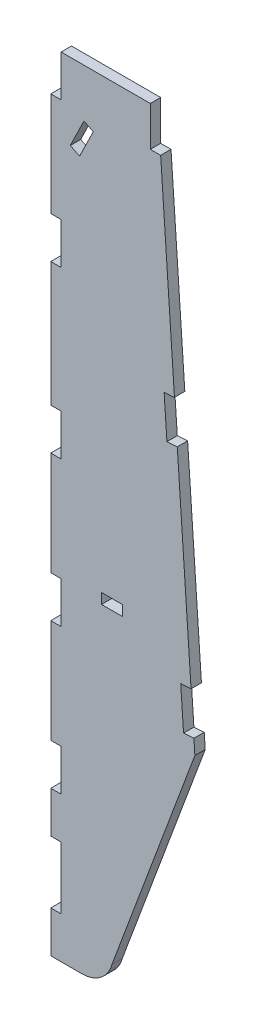
SolidWorks part; units mm, degrees
ref_plane "Plan de face" through (0, 0, 0) normal (0, 0, 1) x (1, 0, 0)
ref_plane "Plan de dessus" through (0, 0, 0) normal (0, 1, 0) x (1, 0, 0)
ref_plane "Plan de droite" through (0, 0, 0) normal (1, 0, 0) x (0, 0, -1)
sketch "Esquisse1" plane through (0, 0, 0) normal (0, 0, 1) x (1, 0, 0)
  line L0 (0, 0) -> (43, 0)
  line L1 (43, 0) -> (43, -19.1614)
  line L2 (43, -19.1614) -> (48, -19.1614)
  line L3 (48, -19.1614) -> (54.6543, -116.9352)
  line L4 (54.6543, -116.9352) -> (49.6659, -117.2748)
  line L5 (49.6659, -117.2748) -> (51.0239, -137.2286)
  line L6 (51.0239, -137.2286) -> (56.0123, -136.8891)
  line L7 (-5, -20) -> (-5, -70)
  line L8 (56.0123, -136.8891) -> (62.6667, -234.6629)
  line L9 (62.6667, -234.6629) -> (57.6782, -235.0024)
  line L10 (57.6782, -235.0024) -> (59.0362, -254.9563)
  line L11 (-5, -70) -> (0, -70)
  line L12 (0, -70) -> (0, -90)
  line L13 (0, 0) -> (0, -20)
  line L14 (0, -20) -> (-5, -20)
  line L15 (0, -90) -> (-5, -90)
  line L16 (-5, -90) -> (-5, -150)
  line L17 (10, -380) -> (10, -365) construction
  line L18 (10, -365) -> (24.4889, -368.8823) construction
  line L19 (0, -220) -> (19.5, -220) construction
  line L20 (-5, -150) -> (0, -150)
  line L21 (0, -150) -> (0, -170)
  line L22 (0, -170) -> (-5, -170)
  line L23 (-5, -170) -> (-5, -220)
  line L24 (-5, -220) -> (0, -220)
  line L25 (0, -220) -> (0, -240)
  line L26 (0, -240) -> (-5, -240)
  line L27 (-5, -240) -> (-5, -290)
  line L28 (-5, -290) -> (0, -290)
  line L29 (0, -290) -> (0, -310)
  line L30 (0, -310) -> (-5, -310)
  line L31 (-5, -310) -> (-5, -330)
  line L32 (-5, -330) -> (0, -330)
  line L33 (0, -330) -> (0, -360)
  line L34 (0, -360) -> (-5, -360)
  line L35 (-5, -360) -> (-5, -380)
  line L36 (-5, -380) -> (10, -380)
  line L37 (59.0362, -254.9563) -> (64.0247, -254.6168)
  line L38 (64.0247, -254.6168) -> (64.5, -261.6006)
  line L39 (64.5, -261.6006) -> (24.4889, -368.8823)
  line L40 (19.5, -220) -> (19.5, -221) construction
  line L41 (-5, -56.1583) -> (11.0005, -23.3523) construction
  line L42 (19.5, -221) -> (29.5, -221)
  line L43 (19.5, -221) -> (19.5, -216)
  line L44 (19.5, -216) -> (29.5, -216)
  line L45 (29.5, -221) -> (29.5, -216)
  line L46 (11.0005, -23.3523) -> (4.425, -36.8342)
  line L47 (11.0005, -23.3523) -> (15.4945, -25.5442)
  line L48 (4.425, -36.8342) -> (8.9189, -39.0261)
  line L49 (15.4945, -25.5442) -> (8.9189, -39.0261)
  line L50 (64.5, -261.6006) -> (-5, -261.6006) construction
  line L51 (-5, -261.6006) -> (64.5, -261.6006) construction
  arc A0 (10, -380) -> (24.4889, -368.8823) centre (10, -365) ccw
  dimension "D11" = 15
  dimension "D1" = 43
  dimension "D2" = 5
  dimension "D5" = 20
  dimension "D6" = 30
  dimension "D7" = 50
  dimension "D3" = 60
  dimension "D4" = 98
  dimension "D8" = 7
  dimension "D9" = 114.5
  dimension "D10" = 15
  dimension "D12" = 75
  dimension "D14" = 19.5
  dimension "D15" = 1
  dimension "D16" = 10
  dimension "D17" = 11.5
  dimension "D18" = 26
  dimension "D19" = 36.5
  dimension "D20" = 15
  dimension "D13" = 69.5
extrude "Boss.-Extru.1" add sketch "Esquisse1" along normal blind 5
sketch "Esquisse2" plane through (0, 0, 5) normal (0, 0, 1) x (1, 0, 0)
  line L0 (64.5, -261.6006) -> (-5, -261.6006)
  line L1 (-5, -240) -> (-5, -290) construction
